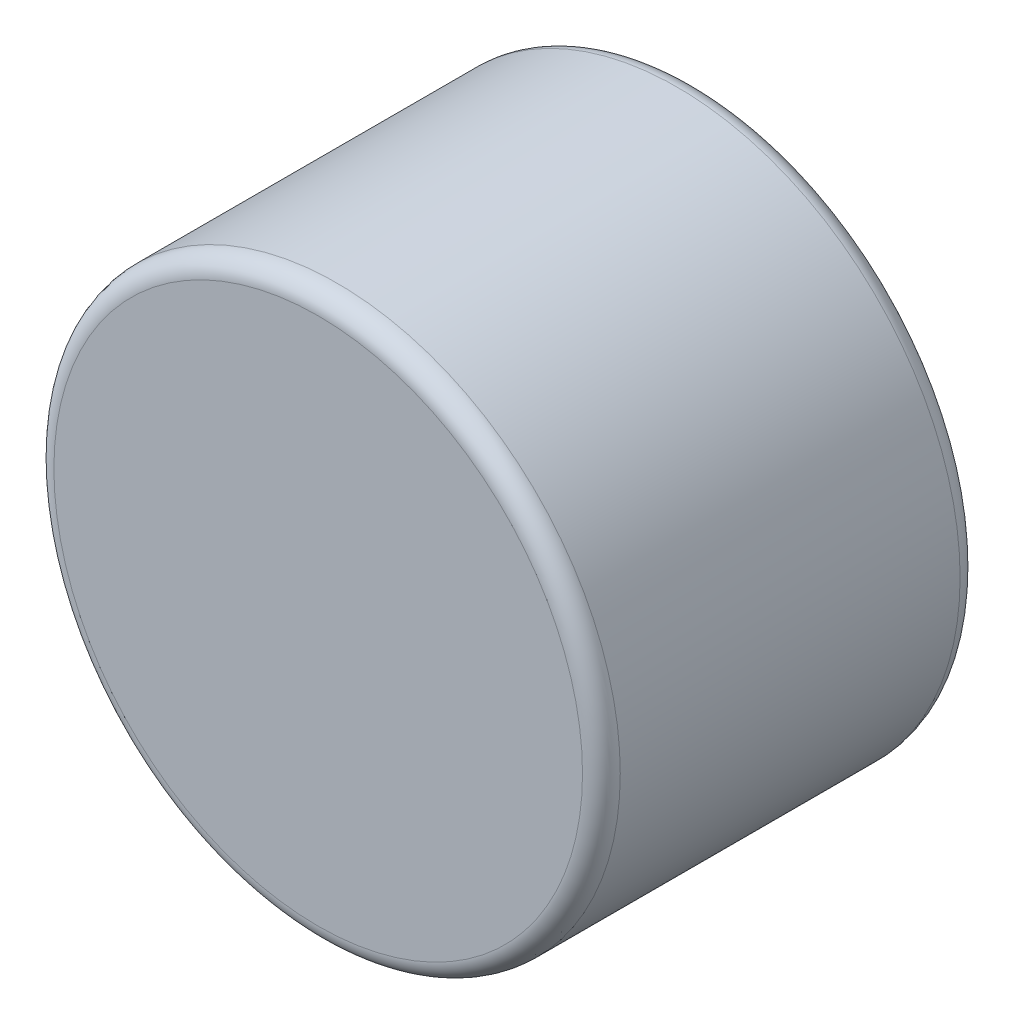
SolidWorks part; units mm, degrees
material "Простая углеродистая сталь"
ref_plane "Front" through (0, 0, 0) normal (0, 0, 1) x (1, 0, 0)
ref_plane "Top" through (0, 0, 0) normal (0, 1, 0) x (1, 0, 0)
ref_plane "Right" through (0, 0, 0) normal (1, 0, 0) x (0, 0, -1)
sketch "Эскиз1" plane through (0, 0, 0) normal (0, 0, 1) x (1, 0, 0)
  circle A0 centre (0, 0) radius 1.5
  dimension "D1" = 3
extrude "Бобышка-Вытянуть1" add sketch "Эскиз1" along normal blind 2
fillet "Скругление1" radius 0.1 2 edges at (1.5, 0, 0) (1.5, 0, 2)
